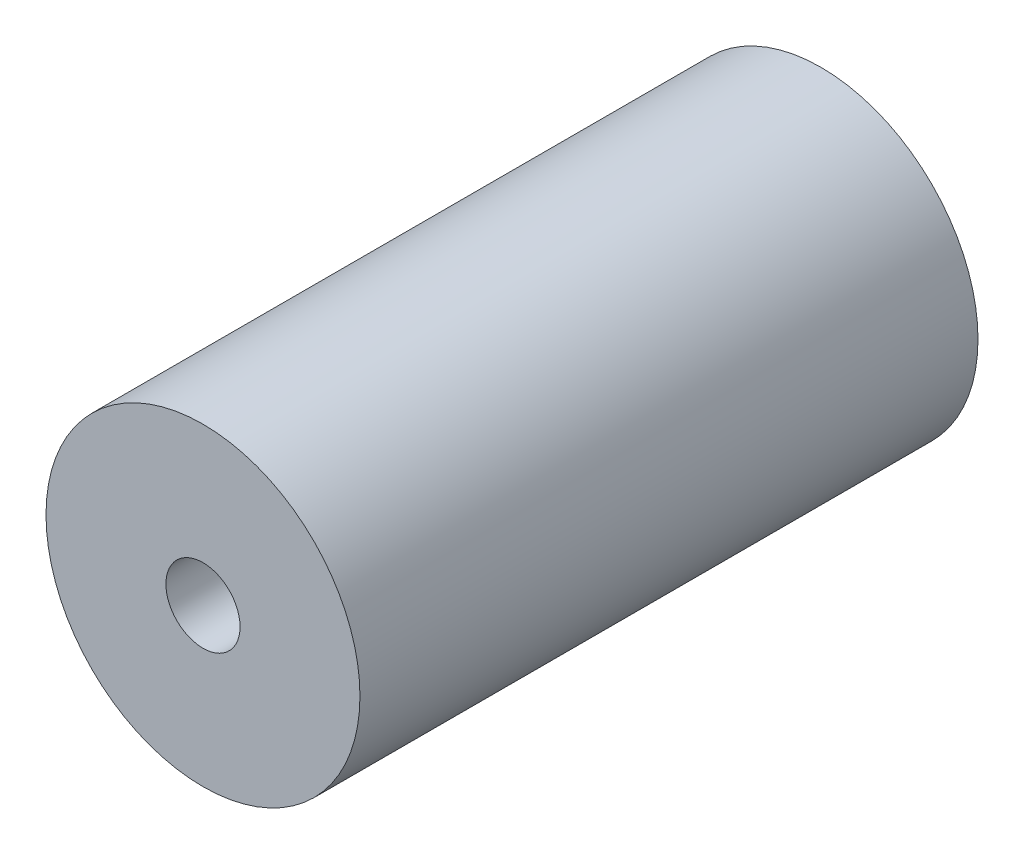
SolidWorks part; units mm, degrees
ref_plane "前视基准面" through (0, 0, 0) normal (0, 0, 1) x (1, 0, 0)
ref_plane "上视基准面" through (0, 0, 0) normal (0, 1, 0) x (1, 0, 0)
ref_plane "右视基准面" through (0, 0, 0) normal (1, 0, 0) x (0, 0, -1)
sketch "Sketch1" plane through (0, 0, 0) normal (0, 0, 1) x (1, 0, 0)
  circle A0 centre (0, 0) radius 12.7
  circle A1 centre (0, 0) radius 3
extrude "Boss-Extrude1" add sketch "Sketch1" along normal blind 50
